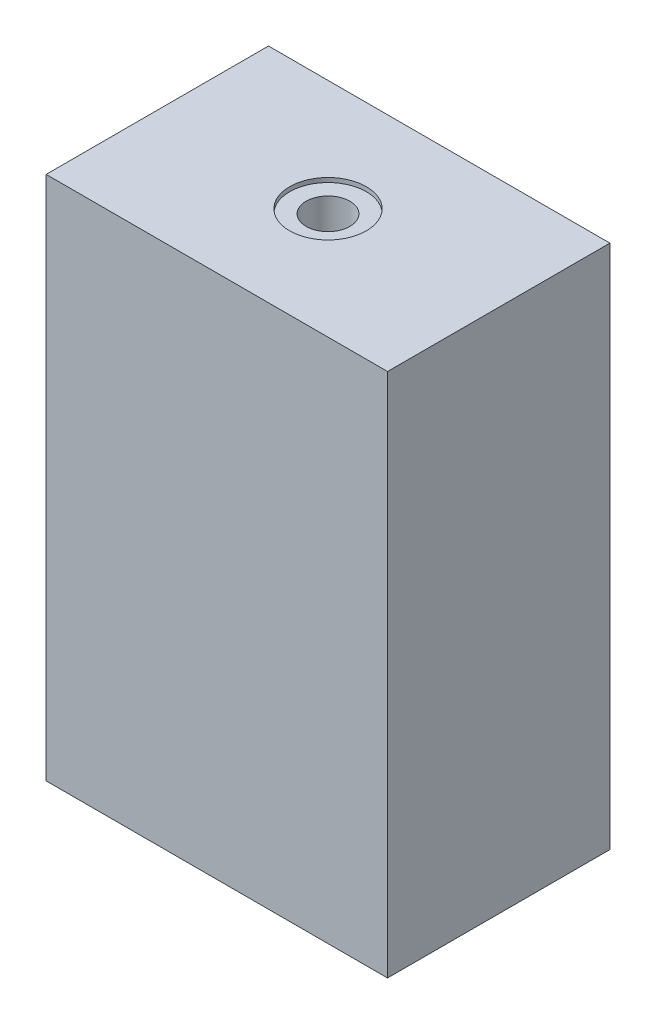
SolidWorks part; units mm, degrees
ref_plane "前视基准面" through (0, 0, 0) normal (0, 0, 1) x (1, 0, 0)
ref_plane "上视基准面" through (0, 0, 0) normal (0, 1, 0) x (1, 0, 0)
ref_plane "右视基准面" through (0, 0, 0) normal (1, 0, 0) x (0, 0, -1)
sketch "草图1" plane through (0, 0, 0) normal (0, 1, 0) x (1, 0, 0)
  line L0 (0, 11.3571) -> (0, -8.6742) construction
  line L1 (-3.9, 2.54) -> (3.9, 2.54)
  line L2 (-3.9, 2.54) -> (-3.9, -2.54)
  line L3 (-3.9, -2.54) -> (3.9, -2.54)
  line L4 (3.9, 2.54) -> (3.9, -2.54)
  line L5 (-11.8577, 0) -> (16.1453, 0) construction
  dimension "D1" = 7.8
  dimension "D2" = 5.08
extrude "拉伸1" add sketch "草图1" along normal blind 12
sketch "草图2" plane through (0, 12, 0) normal (0, 1, 0) x (1, 0, 0)
  line L0 (-4.7448, 0) -> (6.3035, 0) construction
  line L1 (0, 3.5336) -> (0, -3.8045) construction
  circle A0 centre (0, 0) radius 0.5
  dimension "D1" = 1
extrude "切除-拉伸1" cut sketch "草图2" against normal through all
sketch "草图3" plane through (0, 12, 0) normal (0, 1, 0) x (1, 0, 0)
  circle A0 centre (0, 0) radius 0.875
  dimension "D1" = 1.75
extrude "切除-拉伸2" cut sketch "草图3" against normal blind 0.1
sketch "草图4" plane through (0, 0, 0) normal (0, -1, 0) x (1, 0, 0)
  line L0 (-5.0739, 0) -> (5.1699, 0) construction
  line L1 (0, 2.8534) -> (0, -4.0002) construction
  line L2 (-3.4, 1) -> (-1.9, 1)
  line L3 (-3.4, 1) -> (-3.4, -1)
  line L4 (-3.4, -1) -> (-1.9, -1)
  line L5 (-1.9, 1) -> (-1.9, -1)
  line L6 (1.9, 1) -> (1.9, -1)
  line L7 (3.4, -1) -> (1.9, -1)
  line L8 (3.4, 1) -> (3.4, -1)
  line L9 (3.4, 1) -> (1.9, 1)
  dimension "D1" = 1.5
  dimension "D2" = 2
  dimension "D3" = 3.8
extrude "切除-拉伸3" cut sketch "草图4" against normal offset from surface (10 mm away) 2 up to face at (0, 12, 0.875)
